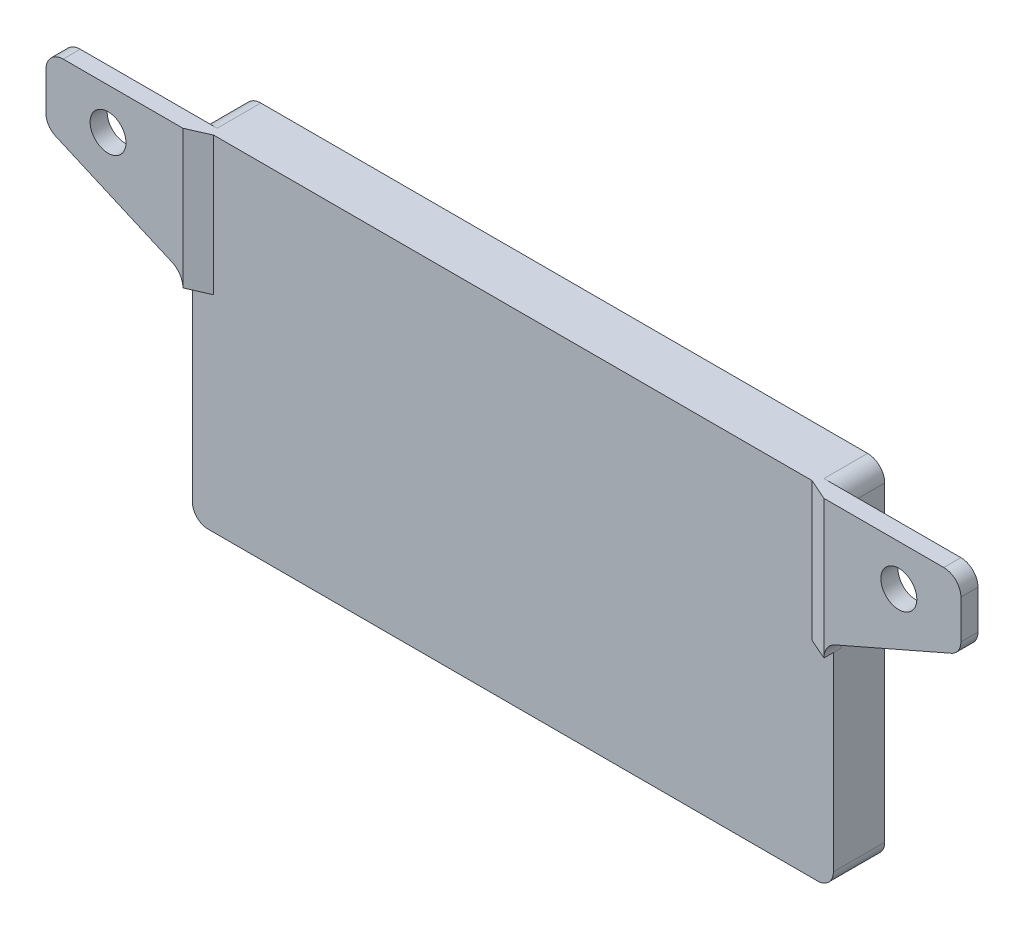
SolidWorks part; units mm, degrees
ref_plane "Front Plane" through (0, 0, 0) normal (0, 0, 1) x (1, 0, 0)
ref_plane "Top Plane" through (0, 0, 0) normal (0, 1, 0) x (1, 0, 0)
ref_plane "Right Plane" through (0, 0, 0) normal (1, 0, 0) x (0, 0, -1)
sketch "Sketch1" plane through (0, 0, 0) normal (0, 0, 1) x (1, 0, 0)
  line L0 (99.95, 149.85) -> (25.05, 149.85)
  line L1 (25.05, 148) -> (25.05, 111.5)
  line L2 (26.9, 109.65) -> (98.1, 109.65)
  line L3 (99.95, 111.5) -> (99.95, 148)
  line L4 (24.9, 148) -> (24.9, 111.5)
  line L5 (26.9, 109.5) -> (98.1, 109.5)
  line L6 (100.1, 111.5) -> (100.1, 148)
  line L7 (102.1, 150) -> (22.9, 150)
  line L8 (24.9, 148) -> (24.9, 111.5) construction
  line L9 (26.9, 109.5) -> (98.1, 109.5) construction
  line L10 (100.1, 111.5) -> (100.1, 148) construction
  line L11 (102.1, 150) -> (22.9, 150) construction
  line L12 (25.05, 148) -> (25.05, 149.85)
  line L14 (101.0046, 149.85) -> (23.9954, 149.85) construction
  line L15 (99.95, 148) -> (99.95, 149.85)
  arc A1 (25.05, 111.5) -> (26.9, 109.65) centre (26.9, 111.5) ccw
  arc A2 (98.1, 109.65) -> (99.95, 111.5) centre (98.1, 111.5) ccw
  arc A4 (24.9, 111.5) -> (26.9, 109.5) centre (26.9, 111.5) ccw
  arc A5 (98.1, 109.5) -> (100.1, 111.5) centre (98.1, 111.5) ccw
  arc A6 (102.1, 150) -> (100.1, 148) centre (102.1, 148) ccw
  arc A7 (24.9, 148) -> (22.9, 150) centre (22.9, 148) ccw
  arc A8 (24.9, 111.5) -> (26.9, 109.5) centre (26.9, 111.5) ccw construction
  arc A9 (98.1, 109.5) -> (100.1, 111.5) centre (98.1, 111.5) ccw construction
  arc A10 (102.1, 150) -> (100.1, 148) centre (102.1, 148) ccw construction
  arc A11 (24.9, 148) -> (22.9, 150) centre (22.9, 148) ccw construction
  arc A16 (25.05, 148) -> (23.9954, 149.85) centre (22.9, 148) ccw construction
  arc A17 (101.0046, 149.85) -> (99.95, 148) centre (102.1, 148) ccw construction
  dimension "D1" = 0
  dimension "D2" = 0.15
extrude "Boss-Extrude1" add sketch "Sketch1" along normal up to surface (5.1 mm away)
sketch "Sketch2" plane through (0, 0, 5.1) normal (0, 0, 1) x (1, 0, 0)
  line L24 (101.2984, 135.5243) -> (114.9016, 141.4757) construction
  line L25 (116.1, 143.308) -> (116.1, 148) construction
  line L26 (118.1, 150) -> (102.1, 150) construction
  line L28 (8.9, 148) -> (8.9, 143.308) construction
  line L29 (10.0984, 141.4757) -> (23.7016, 135.5243) construction
  line L31 (22.9, 150) -> (6.9, 150) construction
  line L32 (101.2984, 135.5243) -> (114.9016, 141.4757) construction
  line L33 (116.1, 143.308) -> (116.1, 148) construction
  line L34 (116.1, 150) -> (102.1, 150) construction
  line L36 (8.9, 148) -> (8.9, 143.308) construction
  line L37 (10.0984, 141.4757) -> (23.7016, 135.5243) construction
  line L39 (22.9, 150) -> (8.9, 150) construction
  line L40 (100.1, 111.5) -> (100.1, 133.692) construction
  line L41 (26.9, 109.5) -> (98.1, 109.5) construction
  line L42 (24.9, 133.692) -> (24.9, 111.5) construction
  line L43 (100.1, 111.5) -> (100.1, 133.692) construction
  line L44 (26.9, 109.5) -> (98.1, 109.5) construction
  line L45 (24.9, 133.692) -> (24.9, 111.5) construction
  line L46 (102.1, 150) -> (22.9, 150) construction
  line L47 (102.1, 150) -> (22.9, 150) construction
  line L48 (8.9, 148) -> (8.9, 150) construction
  line L49 (116.1, 148) -> (116.1, 150) construction
  line L50 (102.1, 149.85) -> (22.9, 149.85)
  line L51 (22.9, 149.85) -> (9.05, 149.85)
  line L52 (9.05, 148) -> (9.05, 149.85)
  line L53 (9.05, 148) -> (9.05, 143.308)
  line L54 (10.1585, 141.6131) -> (23.7618, 135.6617)
  line L55 (25.05, 133.692) -> (25.05, 111.5)
  line L56 (26.9, 109.65) -> (98.1, 109.65)
  line L57 (99.95, 111.5) -> (99.95, 133.692)
  line L58 (101.2382, 135.6617) -> (114.8415, 141.6131)
  line L59 (115.95, 143.308) -> (115.95, 148)
  line L60 (115.95, 148) -> (115.95, 149.85)
  line L61 (115.95, 149.85) -> (102.1, 149.85)
  arc A24 (114.9016, 141.4757) -> (116.1, 143.308) centre (114.1, 143.308) ccw construction
  arc A27 (101.2984, 135.5243) -> (100.1, 133.692) centre (102.1, 133.692) ccw construction
  arc A28 (8.9, 143.308) -> (10.0984, 141.4757) centre (10.9, 143.308) ccw construction
  arc A29 (24.9, 133.692) -> (23.7016, 135.5243) centre (22.9, 133.692) ccw construction
  arc A32 (114.9016, 141.4757) -> (116.1, 143.308) centre (114.1, 143.308) ccw construction
  arc A35 (101.2984, 135.5243) -> (100.1, 133.692) centre (102.1, 133.692) ccw construction
  arc A36 (8.9, 143.308) -> (10.0984, 141.4757) centre (10.9, 143.308) ccw construction
  arc A37 (24.9, 133.692) -> (23.7016, 135.5243) centre (22.9, 133.692) ccw construction
  arc A40 (98.1, 109.5) -> (100.1, 111.5) centre (98.1, 111.5) ccw construction
  arc A41 (24.9, 111.5) -> (26.9, 109.5) centre (26.9, 111.5) ccw construction
  arc A42 (98.1, 109.5) -> (100.1, 111.5) centre (98.1, 111.5) ccw construction
  arc A43 (24.9, 111.5) -> (26.9, 109.5) centre (26.9, 111.5) ccw construction
  arc A44 (9.05, 143.308) -> (10.1585, 141.6131) centre (10.9, 143.308) ccw
  arc A45 (25.05, 133.692) -> (23.7618, 135.6617) centre (22.9, 133.692) ccw
  arc A46 (25.05, 111.5) -> (26.9, 109.65) centre (26.9, 111.5) ccw
  arc A47 (98.1, 109.65) -> (99.95, 111.5) centre (98.1, 111.5) ccw
  arc A48 (101.2382, 135.6617) -> (99.95, 133.692) centre (102.1, 133.692) ccw
  arc A49 (114.8415, 141.6131) -> (115.95, 143.308) centre (114.1, 143.308) ccw
  circle A50 centre (16.3, 145.05) radius 2.1
  circle A51 centre (108.7, 145.05) radius 2.1
  dimension "D2" = 4.2
  dimension "D1" = 0.15
extrude "Boss-Extrude2" add sketch "Sketch2" along normal up to surface (0.9 mm away)
fillet "Fillet1" radius 2 4 edges at (115.95, 149.85, 5.55) (9.05, 149.85, 5.55) (25.05, 149.85, 2.55) (99.95, 149.85, 2.55)
sketch "Sketch3" plane through (0, 0, 6) normal (0, 0, 1) x (1, 0, 0)
  line L0 (99.95, 133.692) -> (99.95, 149.85)
  line L1 (11.05, 149.85) -> (113.95, 149.85) construction
  line L2 (114.8415, 141.6131) -> (101.2382, 135.6617) construction
  line L3 (115.95, 147.85) -> (115.95, 143.308) construction
  line L4 (114.8415, 141.6131) -> (101.2382, 135.6617)
  line L5 (115.95, 147.85) -> (115.95, 143.308)
  line L6 (11.05, 149.85) -> (25.05, 149.85)
  line L7 (25.05, 133.692) -> (25.05, 149.85)
  line L8 (23.7618, 135.6617) -> (10.1585, 141.6131) construction
  line L9 (9.05, 143.308) -> (9.05, 147.85) construction
  line L10 (23.7618, 135.6617) -> (10.1585, 141.6131)
  line L11 (9.05, 143.308) -> (9.05, 147.85)
  line L12 (99.95, 149.85) -> (113.95, 149.85)
  arc A0 (101.2382, 135.6617) -> (99.95, 133.692) centre (102.1, 133.692) ccw construction
  arc A1 (114.8415, 141.6131) -> (115.95, 143.308) centre (114.1, 143.308) ccw construction
  arc A2 (115.95, 147.85) -> (113.95, 149.85) centre (113.95, 147.85) ccw construction
  arc A3 (101.2382, 135.6617) -> (99.95, 133.692) centre (102.1, 133.692) ccw
  arc A4 (114.8415, 141.6131) -> (115.95, 143.308) centre (114.1, 143.308) ccw
  arc A5 (115.95, 147.85) -> (113.95, 149.85) centre (113.95, 147.85) ccw
  arc A6 (25.05, 133.692) -> (23.7618, 135.6617) centre (22.9, 133.692) ccw construction
  arc A7 (9.05, 143.308) -> (10.1585, 141.6131) centre (10.9, 143.308) ccw construction
  arc A8 (11.05, 149.85) -> (9.05, 147.85) centre (11.05, 147.85) ccw construction
  arc A9 (25.05, 133.692) -> (23.7618, 135.6617) centre (22.9, 133.692) ccw
  arc A10 (9.05, 143.308) -> (10.1585, 141.6131) centre (10.9, 143.308) ccw
  arc A11 (11.05, 149.85) -> (9.05, 147.85) centre (11.05, 147.85) ccw
  circle A12 centre (108.7, 145.05) radius 2.1 construction
  circle A13 centre (16.3, 145.05) radius 2.1 construction
  circle A14 centre (108.7, 145.05) radius 2.1
  circle A15 centre (16.3, 145.05) radius 2.1
extrude "Boss-Extrude3" add sketch "Sketch3" along normal offset from surface (1.1 mm away) 2 up to face at (17.4291, 143.8163, 5.1)
sketch "Sketch4" plane through (0, 149.85, 0) normal (0, 1, 0) x (1, 0, 0)
  line L0 (99.95, -7.1) -> (97.45, -6)
  line L1 (25.05, -6) -> (99.95, -6) construction
  line L2 (97.45, -6) -> (99.95, -6)
  line L3 (25.05, -6) -> (25.05, -7.1)
  line L4 (25.05, -7.1) -> (27.55, -6)
  line L5 (27.55, -6) -> (25.05, -6)
  point P11 (26.3529, -6)
  line M6 (25.05, -7.1) -> (25.05, -6)
  line M7 (25.05, -6) -> (99.95, -6)
  line M8 (99.95, -6) -> (99.95, -7.1)
  dimension "D1" = 2.5
extrude "Boss-Extrude4" add sketch "Sketch4" against normal up to vertex (16.158 mm away) contours L4 M6 M7 | L0 M8 M7 region at (25.8833, 149.85, 6.3667) region at (99.1167, 149.85, 6.3667) up to point (25.05, 133.692, 7.1)
equation "\"width\"= 24"
equation "\"thk\"= 3"
equation "\"holesize\"= 4.2"
equation "\"holedistance\"= ( 20 + 12 ) / 2"
equation "\"threaded_hole\"= 3.9"
equation "\"fillet_radius\"= 2"
equation "\"ground_clearance\"= 25"
equation "\"tire_thk\"= 3"
equation "\"innerwheel_diam\" = \"wheel_diam\"-2*\"tire_thk\""
equation "\"innerwheel_thk\"= 8"
equation "\"wheel_diam\"= 2*(\"width\"/2+\"ground_clearance\")"
equation "\"coloursensor_holesize\"= 2.65"
equation "\"hole_to_edge\" = 4"
equation "\"M4_insert_diam\"= 5.7"
